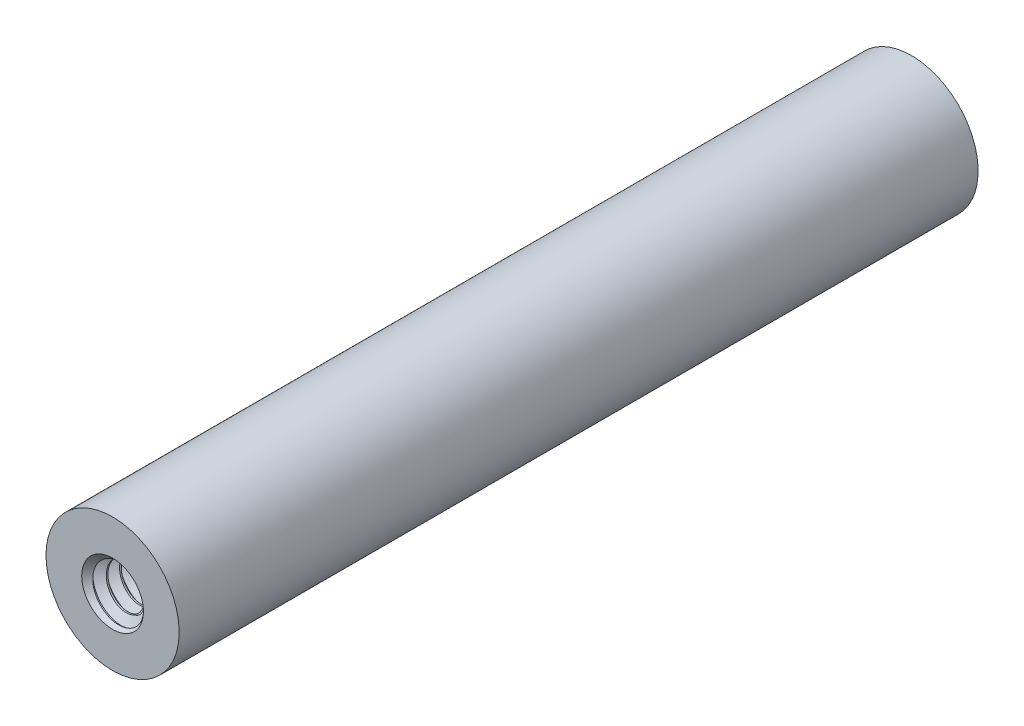
SolidWorks part; units mm, degrees
ref_plane "Front Plane" through (0, 0, 0) normal (0, 0, 1) x (1, 0, 0)
ref_plane "Top Plane" through (0, 0, 0) normal (0, 1, 0) x (1, 0, 0)
ref_plane "Right Plane" through (0, 0, 0) normal (1, 0, 0) x (0, 0, -1)
sketch "Sketch3" plane through (0, 0, 0) normal (1, 0, 0) x (0, 0, -1)
  line L0 (-19.05, 0) -> (19.05, 0) construction
  line L1 (0, 3.175) -> (0, -3.175) construction
  line L2 (-19.05, 1.4224) -> (-19.05, -1.4224) construction
  point P2 (12.7, 0)
  point P3 (-12.7, 0)
  dimension "Length" = 38.1
  dimension "Min Thread Length" = 6.35
  dimension "D1" = 6.35
  dimension "Thread Dia" = 2.8448
  dimension "OD" = 6.35
sketch "Sketch1" plane through (0, 0, 0) normal (0, 0, 1) x (1, 0, 0)
  circle A1 centre (0, 0) radius 1.4224
  circle A2 centre (0, 0) radius 3.175
extrude "Extrude1" add sketch "Sketch1" along normal up to vertex (19.05 mm away) and the other way up to vertex (19.05 mm away) up to point (0, 0, 19.05) other way up to point (0, 0, -19.05)
sketch "Sketch11" plane through (0, 0, -19.05) normal (0, 0, -1) x (-1, 0, 0)
  circle A0 centre (0, 0) radius 1.4224 construction
  circle A1 centre (0, 0) radius 1.4224
curve "Helix/Spiral1" pitch 0.635 height 38.735 radius 1.4224 centre (0, 0, -19.05) axis (0, 0, 1) start towards (0, 1, 0) parameters "Pitch"=0.635
sketch "Sketch12" plane through (0, 0, 0) normal (1, 0, 0) x (0, 0, -1)
  line L0 (19.6056, 1.4224) -> (19.05, 1.4224)
  line L1 (19.6056, 1.4224) -> (19.3675, 1.01)
  line L2 (19.3675, 1.01) -> (19.2881, 1.01)
  line L3 (19.2881, 1.01) -> (19.05, 1.4224)
  line L4 (19.3278, 1.01) -> (19.3278, 1.4224) construction
  line L5 (19.4866, 1.2162) -> (19.1691, 1.2162) construction
  dimension "D1" = 0.0794
  dimension "D2" = 0.3175
  dimension "D3" = 60
sweep "Sweep1" add profiles "Sketch12" path "Helix/Spiral1"
sketch "Sketch6" plane through (0, 0, -19.05) normal (0, 0, -1) x (-1, 0, 0)
  circle A1 centre (0, 0) radius 3.175
  circle A2 centre (0, 0) radius 3.175
  dimension "D1" = 0
extrude "Extrude2" cut sketch "Sketch6" along normal through all
sketch "Sketch7" plane through (0, 0, -19.05) normal (0, 0, -1) x (-1, 0, 0)
  circle A2 centre (0, 0) radius 1.4732
  circle A3 centre (0, 0) radius 1.4732
  dimension "D1" = 0.0508
extrude "Extrude3" cut sketch "Sketch7" against normal through all draft 43
mirror "Mirror1" about plane through (0, 0, 0) normal (0, 0, 1) of "Extrude2", "Extrude3"
sketch "Sketch9" plane through (0, 0, 0) normal (1, 0, 0) x (0, 0, -1)
  line L1 (-12.7, 1.4732) -> (12.7, 1.4732)
  line L2 (-12.7, 1.4732) -> (-12.7, 0)
  line L3 (-12.7, 0) -> (12.7, 0)
  line L4 (12.7, 1.4732) -> (12.7, 0)
  line L7 (-19.05, 0) -> (19.05, 0) construction
revolve "Revolve" add sketch "Sketch9" angle 360 about L0
sketch "Sketch10" plane through (0, 0, 0) normal (1, 0, 0) x (0, 0, -1)
  line L0 (19.05, 1.4224) -> (12.7, 1.4224)
  line L1 (-19.05, 1.4224) -> (-12.7, 1.4224)
  line L2 (12.7, 1.4224) -> (12.7, -1.4224)
  line L3 (-19.05, -1.4732) -> (-12.7, -1.4732)
  line L4 (-12.7, 1.4224) -> (-12.7, -1.4732)
  line L5 (12.7, -1.4224) -> (19.05, -1.4224)
equation "\"D1@Sketch3\" = \"Min Thread Length@Sketch3\""
equation "\"D3@Helix/Spiral1\" = \"Length@Sketch3\"+\"Pitch@Helix/Spiral1\""
equation "\"D1@Sketch12\" = \"Pitch@Helix/Spiral1\"*.125"
equation "\"D2@Sketch12\" = \"Pitch@Helix/Spiral1\"*.5"
